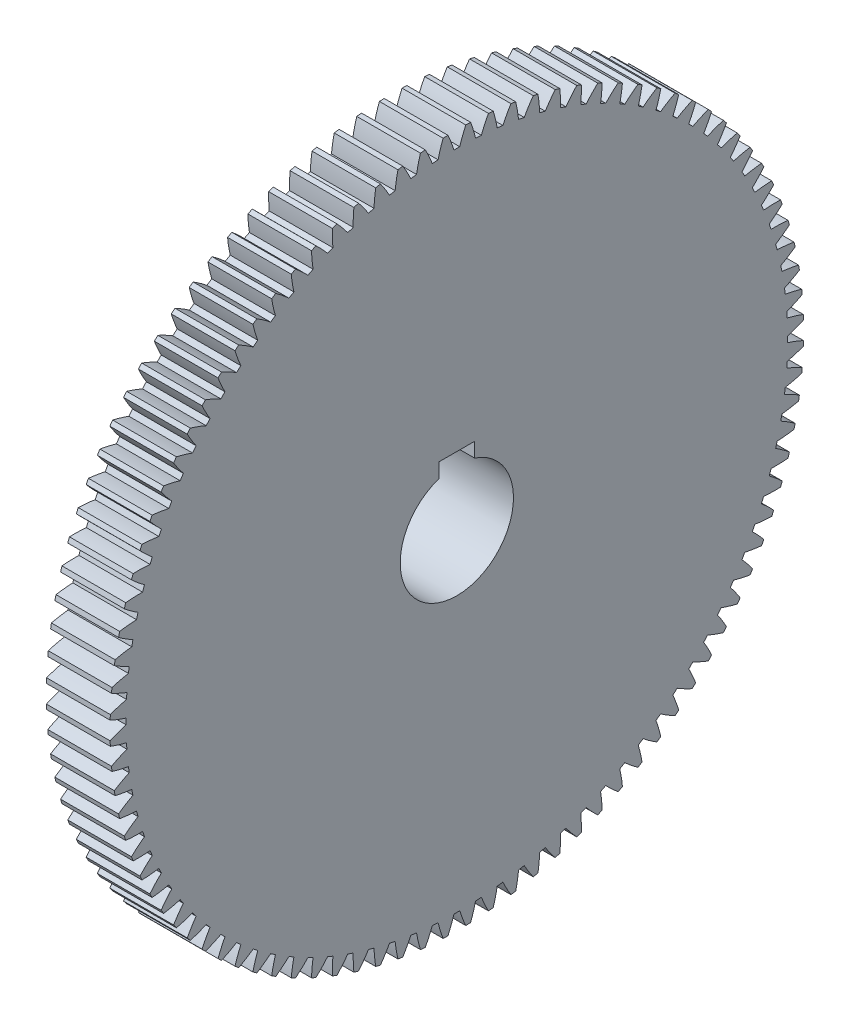
SolidWorks part; units mm, degrees
ref_plane "Plane1" through (0, 0, 0) normal (0, 0, 1) x (1, 0, 0)
ref_plane "Plane2" through (0, 0, 0) normal (0, 1, 0) x (1, 0, 0)
ref_plane "Plane3" through (0, 0, 0) normal (1, 0, 0) x (0, 0, -1)
sketch "HoldingSke" plane through (0, 0, 0) normal (0, 1, 0) x (1, 0, 0)
  line L0 (0, 0) -> (-0.0523, -0.4973)
  line L1 (-15, 0) -> (100, 0) construction
  line L2 (0, 0) -> (-2.1039, 2.3779)
  line L3 (0, 0) -> (-11.863, 4.5341)
  line L4 (0, 0) -> (-0.9027, 8.5887)
  line L5 (0, 0) -> (-28.1086, -10.4837)
  line L6 (0, 0) -> (-14.9213, -10.0675)
  line L7 (-2.1039, 2.3779) -> (4.3536, 31.6747)
  line L8 (-76.2, 54.61) -> (-72.9, 54.61)
  line L9 (-71.009, 38.7566) -> (-53.1078, 45.2721)
  line L10 (-76.2, 71.12) -> (104.1128, 71.12)
  line L11 (0, 0) -> (-18, 0)
  line L12 (-76.2, 101.6) -> (-76.133, 101.6)
  line L13 (24.9733, 27.94) -> (52.9518, 28.4284)
  line L14 (24.9733, 27.94) -> (24.9743, 27.94)
  line L15 (24.9733, 27.94) -> (100.4006, 29.5858)
  line L16 (-63.627, -2) -> (-12.827, -2)
  circle A0 centre (0, 0) radius 16
  circle A1 centre (0, 0) radius 30
  circle A2 centre (0, 0) radius 30
  circle A3 centre (0, 0) radius 16
  dimension "Num_teeth" = 96
  dimension "Pitch_radius" = 180.3128
  dimension "Width" = 18
  dimension "Thickness" = 18
sketch "BasProSke" plane through (0, 0, 0) normal (0, 1, 0) x (1, 0, 0)
  line L0 (-10, 0) -> (60, 0) construction
  line L1 (0, 0) -> (0, 98)
  line L2 (0, 0) -> (18, 0)
  line L3 (18, 0) -> (18, 98)
  line L4 (18, 98) -> (0, 98)
  dimension "Thickness" = 18
  dimension "Diameter" = 196
revolve "Base-Revolve" add sketch "BasProSke" angle 360 about L0
sketch "TooCutSke" plane through (0, 0, 0) normal (1, 0, 0) x (0, 0, -1)
  line L1 (0, 0) -> (0, 107) construction
  line L2 (0, 0) -> (-1.688, 95.9852) construction
  line L3 (0, 0) -> (-6.2813, 191.8752) construction
  line L4 (-1.688, 95.9852) -> (-3.1407, 95.9376) construction
  arc A0 (0.8163, 93.4954) -> (-0.8163, 93.4954) centre (0, 0) ccw
  arc A1 (2.5355, 97.9926) -> (-2.5355, 97.9926) centre (0, 0) ccw
  circle A2 centre (0, 0) radius 96 construction
  circle A3 centre (0, 0) radius 90.2105 construction
  arc A4 (-0.8163, 93.4954) -> (-2.5355, 97.9926) centre (-37.4737, 82.0589) ccw
  arc A5 (2.5355, 97.9926) -> (0.8163, 93.4954) centre (37.4737, 82.0589) ccw
extrude "ToothCut" cut sketch "TooCutSke" along normal through all
fillet "Breaks" [suppressed] radius 0.04 tangent propagation no
fillet "RootFillets" [suppressed] radius 0.501
pattern_circular "TeethCuts" count 96 over 360 about axis through (-10, 0, 0) along (1, 0, 0) of "ToothCut", "RootFillets", "Breaks"
sketch "HubNeaOneSke" plane through (0, 0, 0) normal (-1, 0, 0) x (0, 0, 1)
  circle A0 centre (0, 0) radius 30
  dimension "Diameter" = 60
extrude "HubNearOne" add sketch "HubNeaOneSke" along normal blind 13.5
sketch "HubNeaBotSke" plane through (0, 0, 0) normal (-1, 0, 0) x (0, 0, 1)
  circle A0 centre (0, 0) radius 30
  dimension "Diameter" = 60
extrude "HubNearBoth" [suppressed] add sketch "HubNeaBotSke" along normal blind 6
ref_plane "FarPln" through (18, 0, 0) normal (1, 0, 0) x (0, 0, -1)
sketch "HubFarSke" plane through (18, 0, 0) normal (1, 0, 0) x (0, 0, -1)
  circle A0 centre (0, 0) radius 30
  dimension "Diameter" = 60
extrude "HubFar" [suppressed] add sketch "HubFarSke" along normal blind 6
sketch "BorSke" plane through (0, 0, 0) normal (1, 0, 0) x (0, 0, -1)
  circle A0 centre (0, 0) radius 16
  dimension "Diameter" = 32
extrude "Bore" cut sketch "BorSke" along normal mid plane 60.0001
sketch "KeySke" plane through (0, 0, 0) normal (1, 0, 0) x (0, 0, -1)
  line L0 (-5, 0) -> (-5, 19.3)
  line L1 (-5, 19.3) -> (5, 19.3)
  line L2 (5, 19.3) -> (5, 0)
  line L3 (0, 0) -> (0, 34) construction
  line L4 (-5, 0) -> (5, 0)
  dimension "Width" = 10
extrude "Keyway" cut sketch "KeySke" along normal mid plane 60.0001
pattern_circular "Keyway2" [suppressed] count 2 every 90 about axis through (-10, 0, 0) along (1, 0, 0) reverse direction yes
equation "' \"Module@HoldingSke\" = 6.35"
equation "' \"Num_teeth@HoldingSke\" = 12"
equation "' \"Ap@HoldingSke\" =  20"
equation "' \"Ap@HoldingSke\" = 20"
equation "' \"Width@HoldingSke\" = 0.5 * 25.4"
equation "' \"Hub_dia@HoldingSke\"= 1 * 25.4"
equation "' \"Hub_dia@HoldingSke\" = 1 * 25.4"
equation "' \"Overall_len@HoldingSke\" = 1.0 * 25.4"
equation "' \"Bore@HoldingSke\" = 0.75 * 25.4"
equation "' \"T_dim@HoldingSke\" = 0.1 * 25.4"
equation "' \"Width@KeySke\" = 0.25 * 25.4"
equation "' \"Show_teeth@HoldingSke\" = 13"
equation "' \"Backlash@HoldingSke\" = 0.009 * 25.4"
equation "' \"Addendum_fac@HoldingSke\" = 1.0"
equation "' \"Dedendum_fac@HoldingSke\" = 1.25"
equation "' \"Dedendum_add@HoldingSke\" = 0.00005 * 25.4"
equation "' \"Clearance_fac@HoldingSke\" = 0.25"
equation "\"Pitch@HoldingSke\" = 1 / \"Module@HoldingSke\""
equation "\"Overcut_dia@TooCutSke\" = (\"Num_teeth@HoldingSke\" + 2 * \"Addendum_fac@HoldingSke\") / \"Pitch@HoldingSke\" + 0.002 * 25.4"
equation "\"Pitch_dia@TooCutSke\" = \"Num_teeth@HoldingSke\" / \"Pitch@HoldingSke\""
equation "\"Base_dia@TooCutSke\" = \"Num_teeth@HoldingSke\" / \"Pitch@HoldingSke\" * cos((\"Ap@HoldingSke\"  * 3.14159265 / 180))"
equation "\"Root_dia@TooCutSke\" = (\"Num_teeth@HoldingSke\" + 2) / \"Pitch@HoldingSke\" - 2 * (\"Addendum_fac@HoldingSke\" + \"Dedendum_fac@HoldingSke\") / \"Pitch@HoldingSke\" - \"Dedendum_add@HoldingSke\" * 2"
equation "\"Half_ang@TooCutSke\" = 180 / \"Num_teeth@HoldingSke\""
equation "\"Half_CT@TooCutSke\" = \"Num_teeth@HoldingSke\" / \"Pitch@HoldingSke\" * sin((3.14159265 / 2 / \"Num_teeth@HoldingSke\")) / 2 - 7 * \"Backlash@HoldingSke\" / 4"
equation "\"Flank_rad@TooCutSke\" = \"Num_teeth@HoldingSke\" / \"Pitch@HoldingSke\" / 5"
equation "\"Radius@RootFillets\" = \"Clearance_fac@HoldingSke\" / \"Pitch@HoldingSke\" + \"Dedendum_add@HoldingSke\""
equation "\"Break_rad@Breaks\" = 0.02 / \"Pitch@HoldingSke\""
equation "\"Thickness@HoldingSke\" = \"Width@HoldingSke\""
equation "\"OAL@HoldingSke\" = \"Thickness@HoldingSke\""
equation "\"MHD@HoldingSke\" = (\"Num_teeth@HoldingSke\" + 2) / \"Pitch@HoldingSke\" - 2 * (\"Addendum_fac@HoldingSke\" + \"Dedendum_fac@HoldingSke\")  / \"Pitch@HoldingSke\" - \"Dedendum_add@HoldingSke\" * 2"
equation "\"MBD@HoldingSke\" = (\"Num_teeth@HoldingSke\" + 2) / \"Pitch@HoldingSke\" - 2 * (\"Addendum_fac@HoldingSke\" + \"Dedendum_fac@HoldingSke\")  / \"Pitch@HoldingSke\" - \"Dedendum_add@HoldingSke\" * 2 - 0.002 * 25.4"
equation "\"MHD@HoldingSke\" = ((sgn( \"MHD@HoldingSke\" - \"Hub_dia@HoldingSke\" )-1)*( \"MHD@HoldingSke\" - \"Hub_dia@HoldingSke\" ))/-2+ \"Hub_dia@HoldingSke\""
equation "\"MBD@HoldingSke\" = ((sgn( \"MBD@HoldingSke\" - \"Bore@HoldingSke\" )-1)*( \"MBD@HoldingSke\" - \"Bore@HoldingSke\" ))/-2+ \"Bore@HoldingSke\""
equation "\"OAL@HoldingSke\" = ((sgn( \"OAL@HoldingSke\" - \"Overall_len@HoldingSke\" )+1)*( \"OAL@HoldingSke\" - \"Overall_len@HoldingSke\" ))/2 + \"Overall_len@HoldingSke\" + 0.000002 * 25.4"
equation "\"Num_teeth@TeethCuts\" = int( \"Show_teeth@HoldingSke\" ) + 1"
equation "\"Num_teeth@TeethCuts\" = ((sgn( \"Num_teeth@TeethCuts\" - \"Num_teeth@HoldingSke\" )-1)*( \"Num_teeth@TeethCuts\" - \"Num_teeth@HoldingSke\" ))/-2+ \"Num_teeth@HoldingSke\""
equation "\"Num_teeth@TeethCuts\" = ((sgn( \"Num_teeth@TeethCuts\" - 2.0)+1)*( \"Num_teeth@TeethCuts\" - 2.0))/2 +2.0"
equation "\"Angle@TeethCuts\" = 360.0 / \"Num_teeth@HoldingSke\""
equation "\"Diameter@BasProSke\" = (\"Num_teeth@HoldingSke\" + 2 * \"Addendum_fac@HoldingSke\") / \"Pitch@HoldingSke\""
equation "\"Thickness@BasProSke\"  = \"Thickness@HoldingSke\""
equation "' \"Fillet_rad@BasProSke\" =  \"Thickness@HoldingSke\" * 0.05"
equation "' \"Fillet_rad@BasProSke\" = \"Thickness@HoldingSke\" * 0.05"
equation "\"MHD@HoldingSke\" = ((sgn( \"MHD@HoldingSke\" - \"Root_dia@TooCutSke\" )-1)*( \"MHD@HoldingSke\" - \"Root_dia@TooCutSke\" ))/-2+ \"Root_dia@TooCutSke\""
equation "\"Diameter@HubNeaOneSke\" = \"MHD@HoldingSke\""
equation "\"Diameter@HubNeaBotSke\" = \"MHD@HoldingSke\""
equation "\"Length@HubNearBoth\" = ( \"OAL@HoldingSke\" - \"Thickness@BasProSke\" ) / 2.0"
equation "\"Thickness@FarPln\" = \"Thickness@BasProSke\""
equation "\"Diameter@HubFarSke\" = \"MHD@HoldingSke\""
equation "\"Length@HubFar\" = ( \"OAL@HoldingSke\" - \"Thickness@BasProSke\" ) / 2.0"
equation "\"Diameter@BorSke\" = \"MBD@HoldingSke\""
equation "\"D1@Bore\" = \"OAL@HoldingSke\" * 2.0"
equation "\"D1@Keyway\" = \"OAL@HoldingSke\" * 2.0"
equation "\"Offset@KeySke\" = \"T_dim@HoldingSke\" + \"MBD@HoldingSke\" / 2.0"
